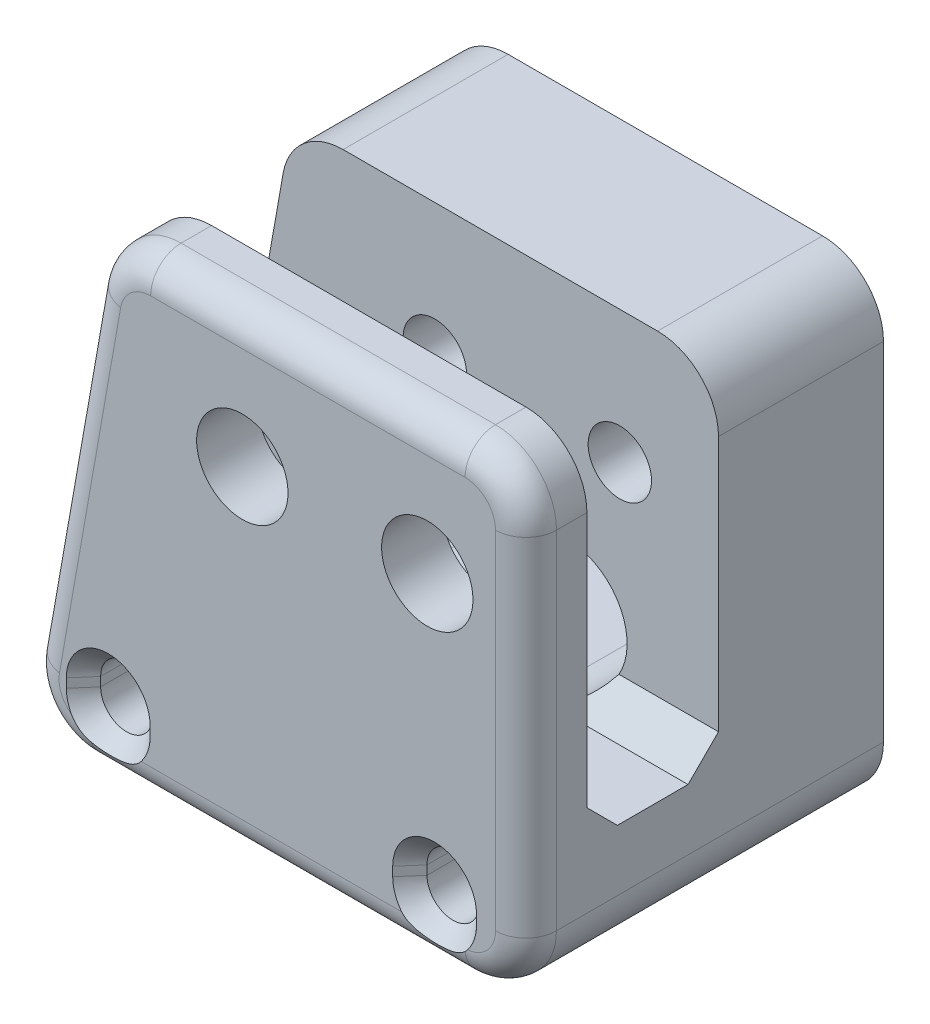
SolidWorks part; units mm, degrees
material "PET"
ref_plane "Front Plane" through (0, 0, 0) normal (0, 0, 1) x (1, 0, 0)
ref_plane "Top Plane" through (0, 0, 0) normal (0, 1, 0) x (1, 0, 0)
ref_plane "Right Plane" through (0, 0, 0) normal (1, 0, 0) x (0, 0, -1)
sketch "Sketch1" plane through (0, 0, 0) normal (0, 0, 1) x (1, 0, 0)
  line L0 (9.9949, 9.271) -> (9.9949, -24.688) construction
  line L2 (9.9949, 9.271) -> (9.9949, -15.163)
  line L3 (9.9949, 9.271) -> (-12.2301, 9.271)
  line L4 (-12.2301, 9.271) -> (-16.5385, -15.163)
  line L5 (-16.5385, -15.163) -> (9.9949, -15.163)
  dimension "D1" = 9.525
  dimension "D2" = 80
  dimension "D3" = 22.225
extrude "Boss-Extrude1" add sketch "Sketch1" along normal blind 3.175
extrude "Boss-Extrude2" add sketch "Sketch1<2>" against normal up to surface (8.5979 mm away) from offset 6.858 separate body offset against normal yes
sketch "Sketch1<2>" plane through (0, 0, 0) normal (0, 0, 1) x (1, 0, 0) same geometry as "Sketch1"
sketch "Sketch3" plane through (0, 0, -6.858) normal (0, 0, 1) x (1, 0, 0)
  line L0 (9.9949, 9.271) -> (9.9949, -15.163) construction
  line L1 (-16.5385, -15.163) -> (-12.2301, 9.271) construction
  line L2 (9.9949, -15.163) -> (-16.5385, -15.163) construction
  line L3 (9.9949, -8.813) -> (9.9949, -15.163)
  line L4 (-16.5385, -15.163) -> (-15.4188, -8.813)
  line L5 (9.9949, -15.163) -> (-16.5385, -15.163)
  line L6 (9.9949, -8.813) -> (-15.4188, -8.813)
  dimension "D1" = 6.35
extrude "Boss-Extrude3" add sketch "Sketch3" along normal up to surface (6.858 mm away) up to face at (-2.1947, -2.946, 0)
hole_wizard "CSK SLOT for #2 Flat Head Machine Screw1" positions "Sketch4" profile "Sketch5" size "#2" standard "ANSI Inch" slot yes end condition through all
sketch "Sketch4" plane through (0, 0, 3.175) normal (0, 0, 1) x (1, 0, 0)
  line L0 (5.2324, -13.5755) -> (5.2324, -10.4005) construction
  line L1 (9.9949, -15.163) -> (9.9949, 9.271) construction
  line L2 (-16.5385, -15.163) -> (9.9949, -15.163) construction
  point P0 (5.2324, -11.988)
  point P2 (-11.776, -11.988)
  dimension "D1" = 3.175
  dimension "D2" = 3.175
  dimension "D3" = 4.7625
  dimension "D4" = 4.7625
sketch "Sketch5" plane through (5.2324, -11.988, 3.175) normal (1, 0, 0) x (0, -1, 0)
  line L0 (0, 0) -> (0, 18.6309)
  line L1 (0, 18.6309) -> (1.3525, 18.6309)
  line L2 (1.3525, 18.6309) -> (1.3525, 0.9569)
  line L3 (1.3525, 0.9569) -> (2.1844, 0)
  line L5 (2.1844, 0) -> (0, 0)
  line L6 (-1.3525, 0.9569) -> (-2.1844, 0) construction
  line L11 (0, -6.35) -> (0, 107.95) construction
  dimension "Thru Hole Dia." = 2.7051
  dimension "Thru Hole Depth" = 18.6309
  dimension "Near C'Sink Dia." = 4.3688
  dimension "Near C'Sink Angle" = 82
fillet "Fillet1" radius 3.175 6 edges at (-12.2301, 9.271, -11.157) (-12.2301, 9.271, 1.5875) (9.9949, 9.271, 1.5875) (9.9949, 9.271, -11.157) (9.9949, -15.163, -6.1405) (-16.5385, -15.163, -6.1405)
chamfer "Chamfer1" distance 1.5875 angle 45 2 edges at (-2.7119, -8.813, 0) (-2.7119, -8.813, -6.858)
hole_wizard "3/16 (0.1875) Diameter Hole1" positions "Sketch6" profile "Sketch7" hole size "3/16" standard "ANSI Inch" end condition up to next
sketch "Sketch6" plane through (0, 0, 3.175) normal (0, 0, 1) x (1, 0, 0)
  point P0 (4.8514, 2.3622)
  point P3 (-4.7879, 2.3622)
sketch "Sketch7" plane through (4.8514, 2.3622, 3.175) normal (1, 0, 0) x (0, -1, 0)
  line L0 (0, 0) -> (0, 3.175)
  line L1 (0, 3.175) -> (2.3812, 3.175)
  line L2 (2.3812, 3.175) -> (2.3812, 0)
  line L5 (2.3812, 0) -> (0, 0)
  line L11 (0, -6.35) -> (0, 107.95) construction
  dimension "Thru Hole Dia." = 4.7625
  dimension "Thru Hole Depth" = 3.175
hole_wizard "#0 Clearance Hole1" positions "Sketch8" profile "Sketch9" hole size "#0" standard "ANSI Inch" end condition up to next
sketch "Sketch8" plane through (0, 0, -15.4559) normal (0, 0, -1) x (-1, 0, 0)
  circle A0 centre (4.7879, 2.3622) radius 2.3812 construction
  circle A1 centre (-4.8514, 2.3622) radius 2.3812 construction
  point P0 (-4.8514, 2.3622)
  point P2 (4.7879, 2.3622)
sketch "Sketch9" plane through (4.8514, 2.3622, -15.4559) normal (1, 0, 0) x (0, 1, 0)
  line L0 (0, 0) -> (0, 8.5979)
  line L1 (0, 8.5979) -> (0.9271, 8.5979)
  line L2 (0.9271, 8.5979) -> (0.9271, 0)
  line L5 (0.9271, 0) -> (0, 0)
  line L11 (0, -6.35) -> (0, 107.95) construction
  dimension "Thru Hole Dia." = 1.8542
  dimension "Thru Hole Depth" = 8.5979
hole_wizard "Hole1" positions "Sketch10" profile "Sketch11" legacy
sketch "Sketch10" plane through (0, 0, -6.858) normal (0, 0, 1) x (1, 0, 0)
  point P0 (4.8514, 2.3622)
  point P3 (-4.7879, 2.3622)
sketch "Sketch11" plane through (4.8514, 2.3622, -6.858) normal (1, 0, 0) x (0, -1, 0)
  line L0 (0, 0) -> (0, 3.048)
  line L1 (0, 3.048) -> (1.524, 3.048)
  line L2 (1.524, 3.048) -> (1.651, 0)
  line L3 (1.651, 0) -> (0, 0)
  line L4 (0, 110) -> (0, -10) construction
  dimension "Minor Diameter" = 3.048
  dimension "Depth" = 3.048
  dimension "Major Diameter" = 3.302
sketch "Sketch13" plane through (0, 0, -15.4559) normal (0, 0, -1) x (-1, 0, 0)
  line L0 (-2.0574, -5.638) -> (6.848, -5.638) construction
  line L1 (-2.0574, -2.463) -> (6.848, -2.463)
  line L2 (-2.0574, -8.813) -> (6.848, -8.813)
  line L3 (15.8814, -11.4367) -> (12.6927, 6.6473) construction
  line L4 (-9.9949, 6.096) -> (-9.9949, -11.988) construction
  line L5 (15.4188, -8.813) -> (-9.9949, -8.813) construction
  arc A0 (-2.0574, -2.463) -> (-2.0574, -8.813) centre (-2.0574, -5.638) ccw
  arc A1 (6.848, -8.813) -> (6.848, -2.463) centre (6.848, -5.638) ccw
  point P2 (2.3953, -5.638)
  point P7 (-5.2324, -5.638)
  point P8 (10.023, -5.638)
  dimension "D1" = 4.7625
  dimension "D2" = 4.7625
  dimension "D3" = 6.35
extrude "Cut-Extrude2" cut sketch "Sketch13" against normal up to next
fillet "Fillet3" radius 1.5875 8 edges at (9.065, -14.2331, 3.175) (-2.9674, -15.163, 3.175) (-15.1868, -14.0288, 3.175) (-14.2871, -2.3947, 3.175) (-11.6068, 8.5282, 3.175) (-1.373, 9.271, 3.175) (9.065, 8.3411, 3.175) (9.9949, -2.946, 3.175)
